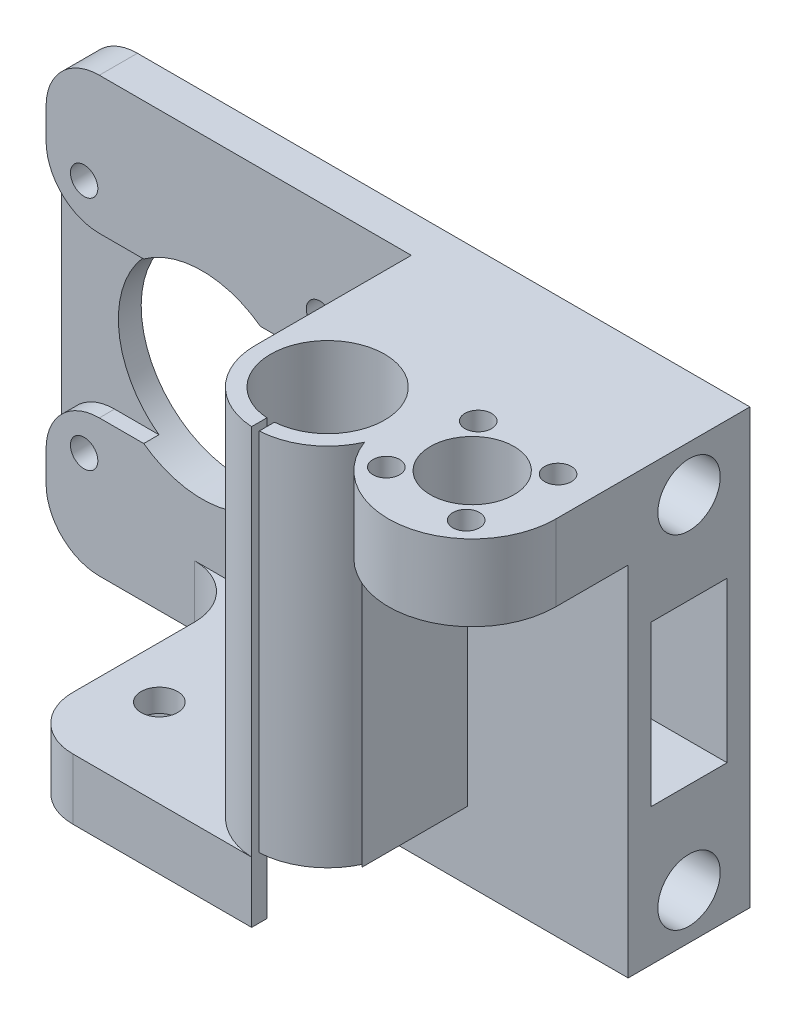
SolidWorks part; units mm, degrees
material "ABS"
ref_plane "Front Plane" through (0, 0, 0) normal (0, 0, 1) x (1, 0, 0)
ref_plane "Top Plane" through (0, 0, 0) normal (0, 1, 0) x (1, 0, 0)
ref_plane "Right Plane" through (0, 0, 0) normal (1, 0, 0) x (0, 0, -1)
sketch "Sketch2" plane through (0, 0, 0) normal (0, 1, 0) x (1, 0, 0)
  line L0 (0, 0) -> (0, -5)
  line L1 (0, -5) -> (48, -5)
  line L2 (48, -5) -> (48, -25.5)
  line L3 (57.5, -25.5) -> (48, -25.5) construction
  line L4 (87.5, -25.5) -> (87.5, 0)
  line L5 (87.5, 0) -> (0, 0)
  line L6 (57.5, -25.5) -> (76.5, -25.5) construction
  line L7 (66.1908, -29.3367) -> (66.1908, -25.5) construction
  line L8 (71.2515, -19.4623) -> (81.7485, -31.5377) construction
  line L9 (82.5377, -20.2515) -> (70.4623, -30.7485) construction
  line L10 (57.5, -25.5) -> (57.5, -34.9868) construction
  line L11 (57, -34.9868) -> (57.5, -34.9868) construction
  line L12 (57.5, -34.9868) -> (58, -34.9868) construction
  line L13 (57, -34.9868) -> (57, -32.9833)
  line L15 (58, -34.9868) -> (58, -32.9833)
  arc A0 (48, -25.5) -> (57, -34.9868) centre (57.5, -25.5) ccw
  circle A1 centre (76.5, -25.5) radius 5.5
  arc A2 (58, -32.9833) -> (57, -32.9833) centre (57.5, -25.5) ccw
  arc A3 (66.1908, -29.3367) -> (87.5, -25.5) centre (76.5, -25.5) ccw
  circle A4 centre (76.5, -25.5) radius 8 construction
  circle A5 centre (70.4623, -30.7485) radius 1.75
  circle A6 centre (82.5377, -20.2515) radius 1.75
  circle A7 centre (71.2515, -19.4623) radius 1.75
  circle A8 centre (81.7485, -31.5377) radius 1.75
  arc A9 (58, -34.9868) -> (66.1908, -29.3367) centre (57.5, -25.5) ccw
  dimension "D5" = 2
  dimension "D8" = 11
  dimension "D9" = 15
  dimension "D10" = 16
  dimension "D1" = 5.5
  dimension "D12" = 41
  dimension "D13" = 3.5
  dimension "D2" = 48
  dimension "D3" = 5
  dimension "D4" = 20.5
  dimension "D7" = 19
  dimension "D14" = 1
extrude "Boss-Extrude1" add sketch "Sketch2" along normal mid plane 57 contours L15 A9 A3 L4 L5 L0 L1 L2 A0 L13 A2 A1 A5 A6 A7 A8 region at (60.1326, 0, 12.0983)
sketch "Sketch3" plane through (0, 0, 0) normal (0, 0, 1) x (1, 0, 0)
  line L0 (0, 0) -> (88, 0) construction
  line L1 (66.4, 18.5) -> (88, 18.5)
  line L2 (66.4, 18.5) -> (66.4, -19.5)
  line L4 (88, 18.5) -> (88, -28.5)
  line L8 (57.1, -19.5) -> (66.4, -19.5)
  line L9 (57.1, -19.5) -> (57.1, -28.5)
  line L10 (57.1, -28.5) -> (88, -28.5)
  dimension "D4" = 47
  dimension "D1" = 88
  dimension "D2" = 18.5
  dimension "D3" = 21.6
  dimension "D5" = 9
  dimension "D6" = 9.3
extrude "Cut-Extrude1" cut sketch "Sketch3" along normal through all from offset 16
sketch "Sketch4" plane through (0, 0, 0) normal (0, 0, 1) x (1, 0, 0)
  line L0 (5, 15.5) -> (36, 15.5) construction
  line L1 (36, 15.5) -> (36, -15.5) construction
  line L2 (36, -15.5) -> (5, -15.5) construction
  line L3 (5, -15.5) -> (5, 15.5) construction
  line L4 (5, -15.5) -> (36, 15.5) construction
  circle A0 centre (5, 15.5) radius 1.8
  circle A1 centre (36, 15.5) radius 1.8
  circle A2 centre (5, -15.5) radius 1.8
  circle A3 centre (36, -15.5) radius 1.8
  circle A4 centre (20.5, 0) radius 13
  dimension "D1" = 31
  dimension "D2" = 3.6
  dimension "D5" = 26
  dimension "D3" = 15.5
  dimension "D4" = 5
extrude "Holes-for-motor" cut sketch "Sketch4" along normal through all
sketch "Sketch5" plane through (0, 0, 0) normal (0, 1, 0) x (1, 0, 0)
  line L0 (57.5, -34.9868) -> (57, -34.9868) construction
  line L1 (26.5, -34.9868) -> (26.5, -4.9868)
  line L2 (57.5, -25.5) -> (57.5, -34.9868) construction
  line L3 (26.5, -4.9868) -> (48, -4.9868)
  line L4 (48, -25.5) -> (48, -4.9868)
  line L5 (26.5, -34.9868) -> (57, -34.9868)
  circle A0 centre (57.5, -25.5) radius 9.5
  dimension "D2" = 19
  dimension "D1" = 31
  dimension "D3" = 57.5
  dimension "D4" = 25.5
  dimension "D5" = 30
  dimension "D6" = 0.5
extrude "Boss-Extrude2" add sketch "Sketch5" against normal blind 8 from offset 20.5 contours A0 L4 L3 L1 region at (37.6225, 0, 20.36) offset against normal yes
sketch "Sketch6" plane through (0, 0, 0) normal (1, 0, 0) x (0, 0, -1)
  line L0 (-3, 0) -> (0, 0) construction
  line L1 (-13, 10.5) -> (-3, 10.5)
  line L2 (-13, 10.5) -> (-13, -10.5)
  line L3 (-13, -10.5) -> (-3, -10.5)
  line L4 (-3, 10.5) -> (-3, -10.5)
  dimension "D1" = 10
  dimension "D2" = 21
  dimension "D3" = 3
extrude "Cut-Extrude3" cut sketch "Sketch6" along normal through all
hole_wizard "M4 Clearance Hole1" positions "Sketch8" profile "Sketch9" hole size "M4" standard "ANSI Metric" end condition through all
sketch "Sketch8" plane through (0, -20.5, 0) normal (0, 1, 0) x (1, 0, 0)
  line L0 (26.5, -34.9868) -> (57, -34.9868) construction
  line L2 (26.5, -34.9868) -> (26.5, -5) construction
  point P0 (33.2838, -23.3998)
  dimension "D1" = 11.587
  dimension "D2" = 6.7838
sketch "Sketch9" plane through (33.2838, -20.5, 23.3998) normal (1, 0, 0) x (0, 0, 1)
  line L0 (0, 0) -> (0, 8)
  line L1 (0, 8) -> (2.4, 8)
  line L2 (2.4, 8) -> (2.4, 0)
  line L5 (2.4, 0) -> (0, 0)
  line L11 (0, -6.35) -> (0, 107.95) construction
  dimension "Thru Hole Dia." = 4.8
  dimension "Thru Hole Depth" = 8
sketch "Sketch10" plane through (0, -20.5, 0) normal (0, 1, 0) x (1, 0, 0)
  line L0 (33.2838, -23.3998) -> (35.6838, -23.3998) construction
  line L1 (39.8407, -23.3998) -> (37.7623, -19.7998)
  line L2 (37.7623, -19.7998) -> (22.7623, -19.7998)
  line L5 (22.7623, -26.9998) -> (37.7623, -26.9998)
  line L6 (37.7623, -26.9998) -> (39.8407, -23.3998)
  line L7 (22.7623, -26.9998) -> (22.7623, -19.7998)
  line L10 (33.0053, -20.8391) -> (31.9661, -22.6391) [skipped]
  line L11 (31.9661, -24.1606) -> (33.0053, -25.9606) [skipped]
  circle A0 centre (35.6838, -23.3998) radius 3.6 construction
  circle A1 centre (33.2838, -23.3998) radius 2.4 construction
  dimension "D1" = 7.2
  dimension "D2" = 15
extrude "Cut-Extrude6" cut sketch "Sketch10" against normal blind 3.4 from offset 3 offset against normal yes
fillet "Fillet1" radius 7 6 edges at (0, -28.5, 2.5) (0, 28.5, 2.5) (26.5, -24.5, 34.9868) (0, 10.5, 4) (0, -10.5, 4) (26.5, -24.5, 5)
sketch "Sketch11" plane through (87.5, 0, 0) normal (1, 0, 0) x (0, 0, -1)
  line L0 (-8, 0) -> (-8, 22.5) construction
  line L1 (-8, -22.5) -> (-8, 0) construction
  line L2 (0, 0) -> (-8, 0) construction
  line L3 (-8, -22.5) -> (-8, -28.5) construction
  line L5 (-16, -28.5) -> (0, -28.5) construction
  circle A0 centre (-8, -22.5) radius 4.1
  circle A1 centre (-8, 22.5) radius 4.1
  dimension "D1" = 45
  dimension "D2" = 8.2
extrude "Cut-Extrude7" cut sketch "Sketch11" against normal blind 21.691
